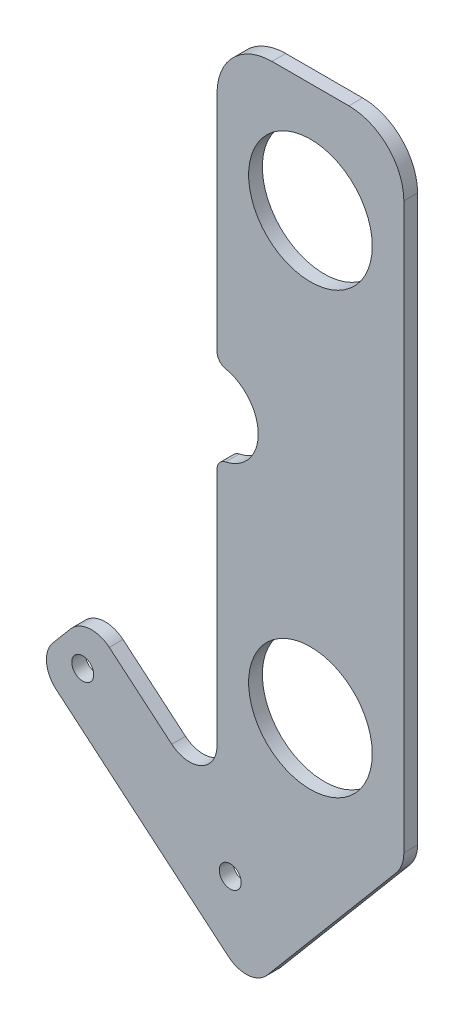
SolidWorks part; units mm, degrees
material "6061 Alloy"
ref_plane "Front Plane" through (0, 0, 0) normal (0, 0, 1) x (1, 0, 0)
ref_plane "Top Plane" through (0, 0, 0) normal (0, 1, 0) x (1, 0, 0)
ref_plane "Right Plane" through (0, 0, 0) normal (1, 0, 0) x (0, 0, -1)
sketch "Sketch1" plane through (0, 0, 0) normal (0, 0, 1) x (1, 0, 0)
  line L0 (0, 0) -> (0, -101.6) construction
  line L1 (21.59, -120.5575) -> (-21.59, -120.5575) construction
  line L2 (-8.89, 25.4) -> (8.89, 25.4)
  line L3 (-21.59, 12.7) -> (-21.59, -117.7751)
  line L5 (21.59, 12.7) -> (21.59, -117.7751)
  line L9 (-23.3829, -122.6853) -> (-33.2033, -134.3394)
  line L10 (-36.322, 25.4) -> (20.828, 25.4) construction
  line L11 (-36.322, 25.4) -> (-36.322, -203.2) construction
  line L12 (-36.322, -203.2) -> (20.828, -203.2) construction
  line L13 (20.828, 25.4) -> (20.828, -203.2) construction
  line L15 (-7.9527, -155.6168) -> (19.7971, -122.6853)
  line L16 (-32.4392, -143.2871) -> (-16.9004, -156.3809)
  circle A0 centre (0, 0) radius 38.1 construction
  circle A1 centre (0, -101.6) radius 38.1 construction
  circle A2 centre (0, 0) radius 14.2875
  circle A3 centre (0, -101.6) radius 14.2875
  arc A6 (8.89, 25.4) -> (21.59, 12.7) centre (8.89, 12.7) cw
  arc A7 (-8.89, 25.4) -> (-21.59, 12.7) centre (-8.89, 12.7) ccw
  circle A10 centre (-18.5321, -142.5501) radius 2.54
  arc A13 (-23.3829, -122.6853) -> (-21.59, -117.7751) centre (-29.21, -117.7751) ccw
  arc A14 (19.7971, -122.6853) -> (21.59, -117.7751) centre (13.97, -117.7751) ccw
  arc A15 (-16.9004, -156.3809) -> (-7.9527, -155.6168) centre (-12.8086, -151.525) ccw
  arc A16 (-33.2033, -134.3394) -> (-32.4392, -143.2871) centre (-28.3474, -138.4312) ccw
  point P12 (-10.8677, -159.0301)
  point P13 (-192.705, 39.2708)
  point P20 (21.59, 25.4)
  point P23 (-21.59, 25.4)
  point P26 (-36.786, -139.4188)
  point P27 (-36.786, -138.7305)
  point P29 (-14.4972, -157.3802)
  point P30 (-14.5377, -157.3461)
  point P31 (-36.322, -138.0404)
  point P32 (-36.9035, -139.0739)
  point P33 (-21.2799, -145.8111)
  point P40 (-10.5599, -158.7108)
  dimension "D2" = 76.2
  dimension "D3" = 76.2
  dimension "D4" = 28.575
  dimension "D5" = 28.575
  dimension "D10" = 228.6
  dimension "D11" = 36.322
  dimension "D13" = 5.08
  dimension "D19" = 6.35
  dimension "D20" = 7.62
  dimension "D21" = 12.7
  dimension "D1" = 101.6
  dimension "D6" = 43.18
  dimension "D7" = 21.59
  dimension "D8" = 25.4
  dimension "D9" = 57.15
  dimension "D12" = 25.4
  dimension "D14" = 33.02
  dimension "D15" = 16.51
  dimension "D16" = 21.59
  dimension "D17" = 9.525
  dimension "D18" = 18.9575
extrude "Boss-Extrude1" add sketch "Sketch1" along normal blind 3.175
sketch "Sketch2" plane through (0, 0, 0) normal (0, 0, 1) x (1, 0, 0)
  line L0 (-21.59, 12.7) -> (-21.59, -117.7751) construction
  line L1 (8.89, 25.4) -> (-8.89, 25.4) construction
  line L2 (-21.59, -41.275) -> (-21.59, -60.325)
  arc A0 (-21.59, -60.325) -> (-21.59, -41.275) centre (-21.59, -50.8) ccw
  dimension "D2" = 19.05
  dimension "D1" = 76.2
extrude "Cut-Extrude1" cut sketch "Sketch2" along normal through all contours L2 A0 region at (-17.5475, -50.8, 0)
fillet "Fillet1" radius 2.54 2 edges at (-21.59, -60.325, 1.5875) (-21.59, -41.275, 1.5875)
sketch "Sketch3" plane through (0, 0, 3.175) normal (0, 0, 1) x (1, 0, 0)
  line L0 (-22.9738, -122.1997) -> (-35.2492, -136.7673)
  line L2 (-9.9986, -158.0447) -> (2.2768, -143.4771)
  line L3 (-7.9527, -155.6168) -> (19.7971, -122.6853) construction
  line L4 (-23.3829, -122.6853) -> (-33.2033, -134.3394) construction
  line L7 (-7.9527, -155.6168) -> (19.7971, -122.6853) construction
  line L8 (-23.3829, -122.6853) -> (-33.2033, -134.3394) construction
  line L10 (-34.4851, -145.715) -> (-18.9463, -158.8088)
  line L11 (-32.4392, -143.2871) -> (-16.9004, -156.3809) construction
  line L12 (-22.9738, -122.1997) -> (2.2768, -143.4771)
  circle A2 centre (-18.5321, -142.5501) radius 2.54
  circle A3 centre (-18.5321, -142.5501) radius 2.54 construction
  arc A4 (-9.9986, -158.0447) -> (-18.9463, -158.8088) centre (-14.8545, -153.9529) cw
  arc A5 (-35.2492, -136.7673) -> (-34.4851, -145.715) centre (-30.3933, -140.8591) ccw
  point P2 (-4.9838, -152.0935)
  point P6 (-29.4972, -129.9412)
  point P21 (-7.2652, -154.801)
  point P26 (0, 0)
  point P27 (0, 0)
  point P28 (-30.9959, -131.7198)
  point P29 (0, 0)
  point P32 (0, 0)
  point P33 (-30.0725, -130.624)
  point P34 (-4.3516, -151.3433)
  point P35 (-5.5032, -152.7099)
  dimension "D2" = 6.35
  dimension "D1" = 3.175
  dimension "D3" = 25.4
extrude "Boss-Extrude3" add sketch "Sketch3" against normal blind 3.175
sketch "Sketch6" plane through (0, 0, 3.175) normal (0, 0, 1) x (1, 0, 0)
  line L0 (-34.4851, -145.715) -> (-63.6204, -121.1641)
  line L1 (-63.6204, -121.1641) -> (-51.345, -106.5965)
  line L2 (-51.345, -106.5965) -> (-27.0656, -127.0555)
  line L3 (-34.4851, -145.715) -> (-18.9463, -158.8088) construction
  line L5 (-23.3829, -122.6853) -> (-35.2492, -136.7673) construction
  line L6 (-34.4851, -145.715) -> (-27.0656, -127.0555)
  circle A0 centre (-52.6268, -117.9721) radius 2.54
  dimension "D4" = 5.08
  dimension "D1" = 31.75
  dimension "D2" = 9.525
  dimension "1" = 19.05
  dimension "D3" = 6.35
extrude "Boss-Extrude4" add sketch "Sketch6" against normal blind 3.175
fillet "Fillet2" radius 6.35 3 edges at (-63.6204, -121.1641, 1.5875) (-51.345, -106.5965, 1.5875) (-27.0656, -127.0555, 1.5875)
